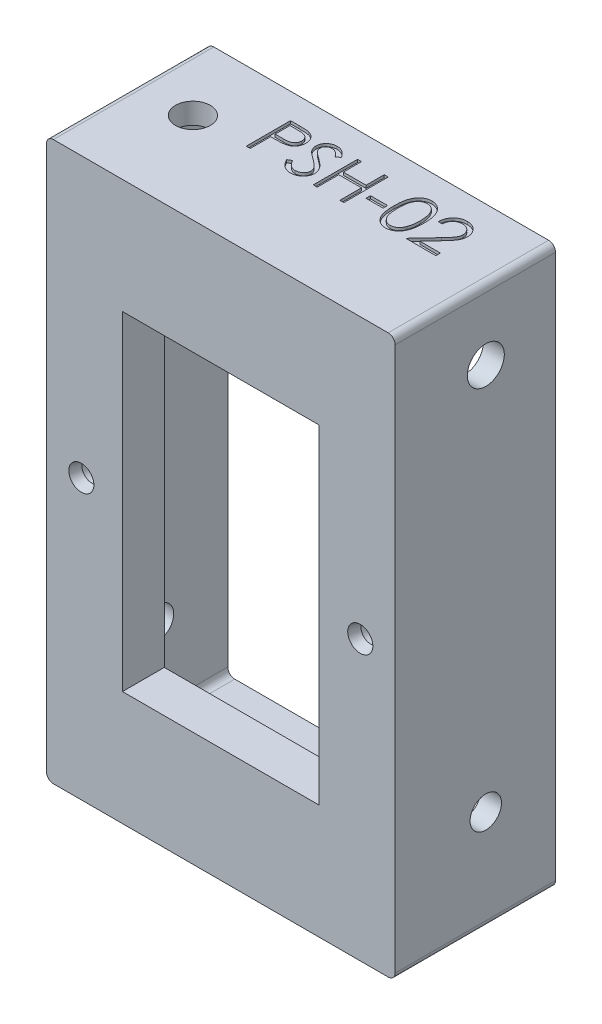
SolidWorks part; units mm, degrees
ref_plane "Front" through (0, 0, 0) normal (0, 0, 1) x (1, 0, 0)
ref_plane "Top" through (0, 0, 0) normal (0, 1, 0) x (1, 0, 0)
ref_plane "Right" through (0, 0, 0) normal (1, 0, 0) x (0, 0, -1)
sketch "Sketch3" plane through (0, 0, 0) normal (0, 0, 1) x (1, 0, 0)
  line L0 (10.9, 16.4) -> (0, 16.4) construction
  line L1 (0, 0) -> (50, 0)
  line L2 (0, 0) -> (0, 80)
  line L3 (0, 80) -> (50, 80)
  line L4 (50, 0) -> (50, 80)
  line L5 (10.9, 16.4) -> (39.1, 16.4)
  line L6 (10.9, 16.4) -> (10.9, 63.6)
  line L7 (10.9, 63.6) -> (39.1, 63.6)
  line L8 (39.1, 16.4) -> (39.1, 63.6)
  line L9 (39.1, 16.4) -> (50, 16.4) construction
  line L10 (10.9, 16.4) -> (10.9, 0) construction
  line L11 (10.9, 63.6) -> (10.9, 80) construction
  line L12 (25, 63.6) -> (25, 40) construction
  line L13 (25, 40) -> (25, 16.4) construction
  line L14 (25, 40) -> (5, 40) construction
  line L15 (25, 40) -> (45, 40) construction
  circle A0 centre (5, 40) radius 1.4
  circle A1 centre (45, 40) radius 1.4
  dimension "D5" = 40
  dimension "D6" = 2.8
  dimension "D1" = 50
  dimension "D2" = 80
  dimension "D3" = 28.2
  dimension "D4" = 47.2
extrude "Boss-Extrude1" add sketch "Sketch3" along normal blind 23
sketch "Sketch4" plane through (0, 0, 0) normal (0, 0, -1) x (-1, 0, 0)
  line L8 (-47, 3) -> (-3, 3)
  line L9 (-3, 3) -> (-3, 77)
  line L10 (-47, 77) -> (-47, 3)
  line L11 (-3, 77) -> (-47, 77)
  line L12 (-47, 3) -> (-3, 3)
  line L13 (-3, 3) -> (-3, 77)
  line L14 (-47, 77) -> (-47, 3)
  line L15 (-3, 77) -> (-47, 77)
  dimension "D1" = 3
extrude "Cut-Extrude1" cut sketch "Sketch4" against normal offset from surface (17 mm away) 6 up to face at (25, 40, 23)
chamfer "Chamfer1" distance 0.4 angle 75 2 edges at (46.4, 40, 23) (6.4, 40, 23) first distance on face at (25, 40, 23)
fillet "Fillet1" radius 1 4 edges at (0, 0, 11.5) (50, 0, 11.5) (50, 80, 11.5) (0, 80, 11.5)
fillet "Fillet2" radius 1 4 edges at (47, 3, 8.5) (3, 3, 8.5) (3, 77, 8.5) (47, 77, 8.5)
sketch "Sketch5" plane through (0, 0, 0) normal (-1, 0, 0) x (0, 0, 1)
  line L0 (0, 79) -> (0, 1) construction
  line L1 (0, 80) -> (23, 80) construction
  line L2 (10, 70) -> (10, 45) construction
  line L3 (10, 45) -> (10, 14.5) construction
  circle A0 centre (10, 70) radius 2.5
  circle A2 centre (10, 14.5) radius 2.25
  dimension "D1" = 10
  dimension "D2" = 5
  dimension "D3" = 10
  dimension "D4" = 25
  dimension "D5" = 14.5
  dimension "D6" = 4.5
extrude "Cut-Extrude2" cut sketch "Sketch5" against normal up to next
hole_wizard "M5 Clearance Hole1" positions "Sketch6" profile "Sketch7" hole size "M5" standard "ANSI Metric" end condition up to next
sketch "Sketch6" plane through (47, 0, 0) normal (-1, 0, 0) x (0, 0, 1)
  point P0 (10, 70)
sketch "Sketch7" plane through (47, 70, 10) normal (0, 1, 0) x (0, 0, 1)
  line L0 (0, 0) -> (0, 3)
  line L1 (0, 3) -> (2.65, 3)
  line L2 (2.65, 3) -> (2.65, 0)
  line L5 (2.65, 0) -> (0, 0)
  line L11 (0, -6.35) -> (0, 107.95) construction
  dimension "Thru Hole Dia." = 5.3
  dimension "Thru Hole Depth" = 3
sketch "Sketch8" plane through (0, 80, 0) normal (0, 1, 0) x (1, 0, 0)
  line L0 (49, 0) -> (1, 0) construction
  line L1 (0, -23) -> (0, 0) construction
  circle A0 centre (8, -10) radius 2.5
  dimension "D1" = 5
  dimension "D3" = 8
  dimension "D2" = 10
extrude "Cut-Extrude3" cut sketch "Sketch8" against normal up to next
hole_wizard "M5 Clearance Hole2" positions "Sketch10" profile "Sketch11" hole size "M5" standard "ANSI Metric" end condition up to next
sketch "Sketch10" plane through (0, 3, 0) normal (0, 1, 0) x (1, 0, 0)
  point P0 (8, -10)
sketch "Sketch11" plane through (8, 3, 10) normal (1, 0, 0) x (0, 0, 1)
  line L0 (0, 0) -> (0, 3)
  line L1 (0, 3) -> (2.65, 3)
  line L2 (2.65, 3) -> (2.65, 0)
  line L5 (2.65, 0) -> (0, 0)
  line L11 (0, -6.35) -> (0, 107.95) construction
  dimension "Thru Hole Dia." = 5.3
  dimension "Thru Hole Depth" = 3
sketch "Sketch12" plane through (47, 0, 0) normal (-1, 0, 0) x (0, 0, 1)
  circle A0 centre (10, 14.5) radius 2.25 construction
  circle A1 centre (10, 14.5) radius 2.25
extrude "Cut-Extrude4" cut sketch "Sketch12" against normal through all
sketch "Sketch13" plane through (0, 80, 0) normal (0, 1, 0) x (1, 0, 0)
  line L0 (8, -10) -> (50, -10) construction
  line L1 (50, 0) -> (50, -23) construction
  text T0 "PSH-02"
extrude "Cut-Extrude5" cut sketch "Sketch13" against normal blind 0.4
sketch "Sketch14" plane through (0, 0, 23) normal (0, 0, 1) x (1, 0, 0)
  line L1 (10.25, 68.5) -> (39.75, 68.5)
  line L2 (10.25, 68.5) -> (10.25, 11.5)
  line L3 (10.25, 11.5) -> (39.75, 11.5)
  line L4 (39.75, 68.5) -> (39.75, 11.5)
  line L6 (25, 68.5) -> (25, 63.6) construction
  line L7 (39.1, 63.6) -> (10.9, 63.6) construction
  line L8 (25, 11.5) -> (25, 16.4) construction
  line L9 (10.9, 16.4) -> (39.1, 16.4) construction
  dimension "D1" = 57
  dimension "D2" = 29.5
extrude "Cut-Extrude6" [suppressed] cut sketch "Sketch14" against normal through all
